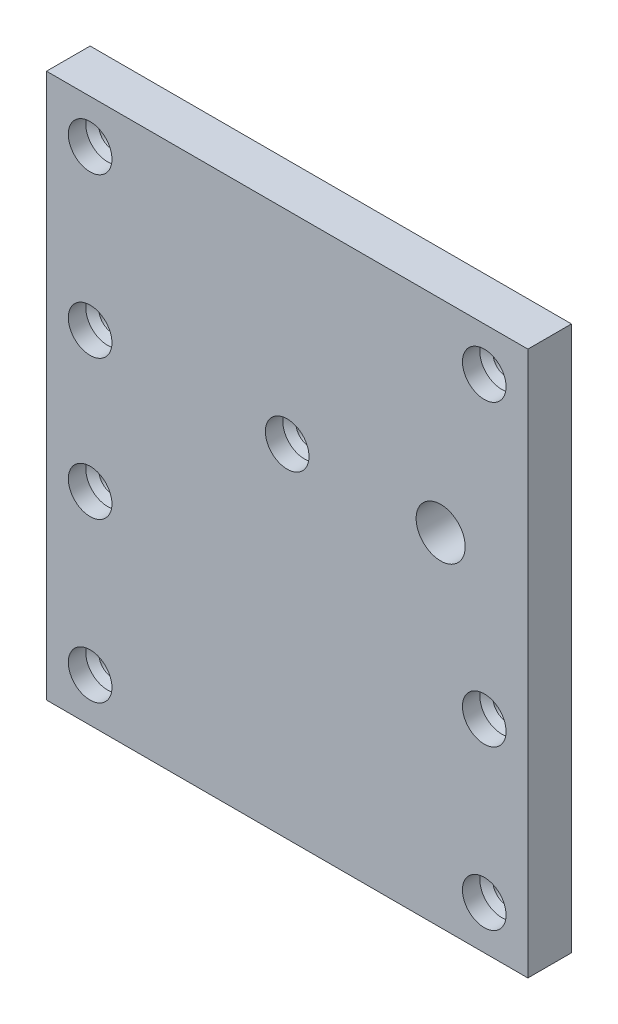
SolidWorks part; units mm, degrees
material "PET"
ref_plane "Front Plane" through (0, 0, 0) normal (0, 0, 1) x (1, 0, 0)
ref_plane "Top Plane" through (0, 0, 0) normal (0, 1, 0) x (1, 0, 0)
ref_plane "Right Plane" through (0, 0, 0) normal (1, 0, 0) x (0, 0, -1)
sketch "Sketch1" plane through (0, 0, 0) normal (0, 0, 1) x (1, 0, 0)
  line L1 (20.3421, 15.5299) -> (-14.7, 15.5299)
  line L2 (20.3421, 15.5299) -> (20.3421, 55.1793)
  line L3 (20.3421, 55.1793) -> (-14.7, 55.1793)
  line L4 (-14.7, 15.5299) -> (-14.7, 55.1793)
extrude "Boss-Extrude1" add sketch "Sketch1" along normal blind 3.175
hole_wizard "9/64 (0.14063) Diameter Hole1" positions "Sketch3" profile "Sketch2" hole size "9/64" standard "ANSI Inch" end condition through all
sketch "Sketch3" plane through (0, 0, 3.175) normal (0, 0, 1) x (1, 0, 0)
  point P0 (13.9921, 40.4346)
sketch "Sketch2" plane through (13.9921, 40.4346, 3.175) normal (1, 0, 0) x (0, -1, 0)
  line L0 (0, 0) -> (0, 3.175)
  line L1 (0, 3.175) -> (1.786, 3.175)
  line L2 (1.786, 3.175) -> (1.786, 0)
  line L5 (1.786, 0) -> (0, 0)
  line L11 (0, -6.35) -> (0, 107.95) construction
  dimension "Thru Hole Dia." = 3.572
  dimension "Thru Hole Depth" = 3.175
hole_wizard "5/64 (0.07813) Diameter Hole1" positions "Sketch5" profile "Sketch4" hole size "5/64" standard "ANSI Inch" end condition through all
sketch "Sketch5" plane through (0, 0, 3.175) normal (0, 0, 1) x (1, 0, 0)
  line L0 (-14.7, 37.2596) -> (20.3421, 37.2596) construction
  line L1 (-14.7, 55.1793) -> (-14.7, 37.2596) construction
  line L2 (2.8211, 55.1793) -> (2.8211, 15.5299) construction
  line L3 (20.3421, 55.1793) -> (-14.7, 55.1793) construction
  line L4 (-14.7, 15.5299) -> (20.3421, 15.5299) construction
  line L5 (2.8211, 35.3546) -> (20.3421, 35.3546) construction
  line L6 (20.3421, 15.5299) -> (20.3421, 55.1793) construction
  point P0 (-11.525, 40.4346)
  point P14 (-11.525, 52.0043)
  point P19 (17.1671, 52.0043)
  point P20 (2.8211, 40.4346)
  point P29 (-11.525, 30.2746)
  point P30 (-11.525, 18.7049)
  point P31 (17.1671, 18.7049)
  point P32 (17.1671, 30.2746)
  dimension "D1" = 3.175
  dimension "D2" = 3.175
  dimension "D3" = 3.175
sketch "Sketch4" plane through (-11.525, 40.4346, 3.175) normal (1, 0, 0) x (0, -1, 0)
  line L0 (0, 0) -> (0, 3.175)
  line L1 (0, 3.175) -> (0.9923, 3.175)
  line L2 (0.9923, 3.175) -> (0.9923, 0)
  line L5 (0.9923, 0) -> (0, 0)
  line L11 (0, -6.35) -> (0, 107.95) construction
  dimension "Thru Hole Dia." = 1.9845
  dimension "Thru Hole Depth" = 3.175
hole_wizard "1/8 (0.125) Diameter Hole1" positions "Sketch7" profile "Sketch8" hole size "1/8" standard "ANSI Inch"
sketch "Sketch7" plane through (0, 0, 3.175) normal (0, 0, 1) x (1, 0, 0)
  point P0 (17.1671, 18.7049)
  point P3 (-11.525, 18.7049)
  point P6 (-11.525, 30.2746)
  point P9 (17.1671, 30.2746)
  point P12 (2.8211, 40.4346)
  point P16 (-11.525, 40.4346)
  point P23 (17.1671, 52.0043)
  point P26 (-11.525, 52.0043)
sketch "Sketch8" plane through (17.1671, 18.7049, 3.175) normal (1, 0, 0) x (0, -1, 0)
  line L0 (0, 0) -> (0, 2.2239)
  line L1 (0, 2.2239) -> (1.5875, 1.27)
  line L2 (1.5875, 1.27) -> (1.5875, 0)
  line L5 (1.5875, 0) -> (0, 0)
  line L10 (0, 2.2239) -> (-1.5875, 1.27) construction
  line L11 (0, -6.35) -> (0, 107.95) construction
  dimension "Hole Dia." = 3.175
  dimension "Hole Depth" = 1.27
  dimension "Drill Angle" = 118
mirror "Mirror1" [suppressed] of bodies 104
delete or keep bodies "Body-Delete/Keep 1" [suppressed] type delete bodies bodies 104
